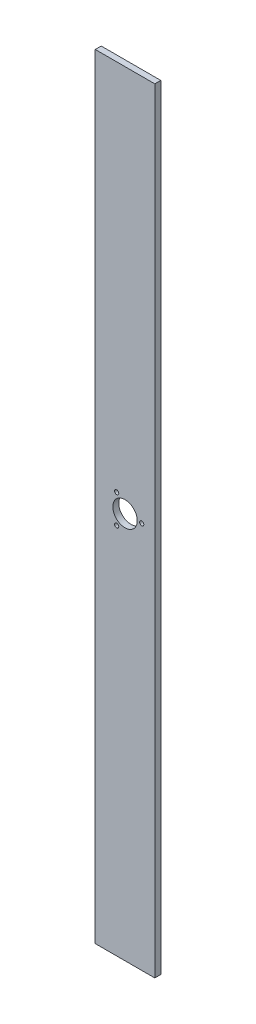
SolidWorks part; units mm, degrees
ref_plane "Plan de face" through (0, 0, 0) normal (0, 0, 1) x (1, 0, 0)
ref_plane "Plan de dessus" through (0, 0, 0) normal (0, 1, 0) x (1, 0, 0)
ref_plane "Plan de droite" through (0, 0, 0) normal (1, 0, 0) x (0, 0, -1)
sketch "Esquisse1" plane through (0, 0, 0) normal (0, 0, 1) x (1, 0, 0)
  line L0 (18, -312.8756) -> (25, -325)
  line L1 (0, 0) -> (50, 0)
  line L2 (0, 0) -> (0, -650)
  line L3 (0, -650) -> (50, -650)
  line L4 (50, 0) -> (50, -650)
  line L5 (25, -325) -> (39, -325)
  line L6 (25, -325) -> (18, -337.1244)
  circle A0 centre (25, -325) radius 10.25
  circle A1 centre (25, -325) radius 14
  circle A3 centre (18, -312.8756) radius 1.75
  circle A4 centre (18, -337.1244) radius 1.75
  circle A5 centre (39, -325) radius 1.75
  dimension "D5" = 20.5
  dimension "D6" = 120
  dimension "D7" = 28
  dimension "D8" = 3.5
  dimension "D9" = 3.5
  dimension "D10" = 3.5
  dimension "D1" = 50
  dimension "D2" = 650
  dimension "D3" = 25
  dimension "D4" = 325
  dimension "D11" = 120
  dimension "D12" = 90
extrude "Boss.-Extru.1" add sketch "Esquisse1" along normal blind 5 contours L4 L1 L2 L3 A5 A1 A4 A3 | A5 A1 A3 L0 A0 L5 | A4 L6 A0 L0 A3 A1 | A5 L5 A0 L6 A4 A1 region at (30.1275, -316.1189, 0) region at (14.7449, -325, 0) region at (30.1275, -333.8811, 0) region at (25, -6.5192, 0)
chamfer "Chanfrein1" distance 1 angle 45 3 edges at (19.75, -337.1244, 0) (19.75, -312.8756, 0) (40.75, -325, 0)
